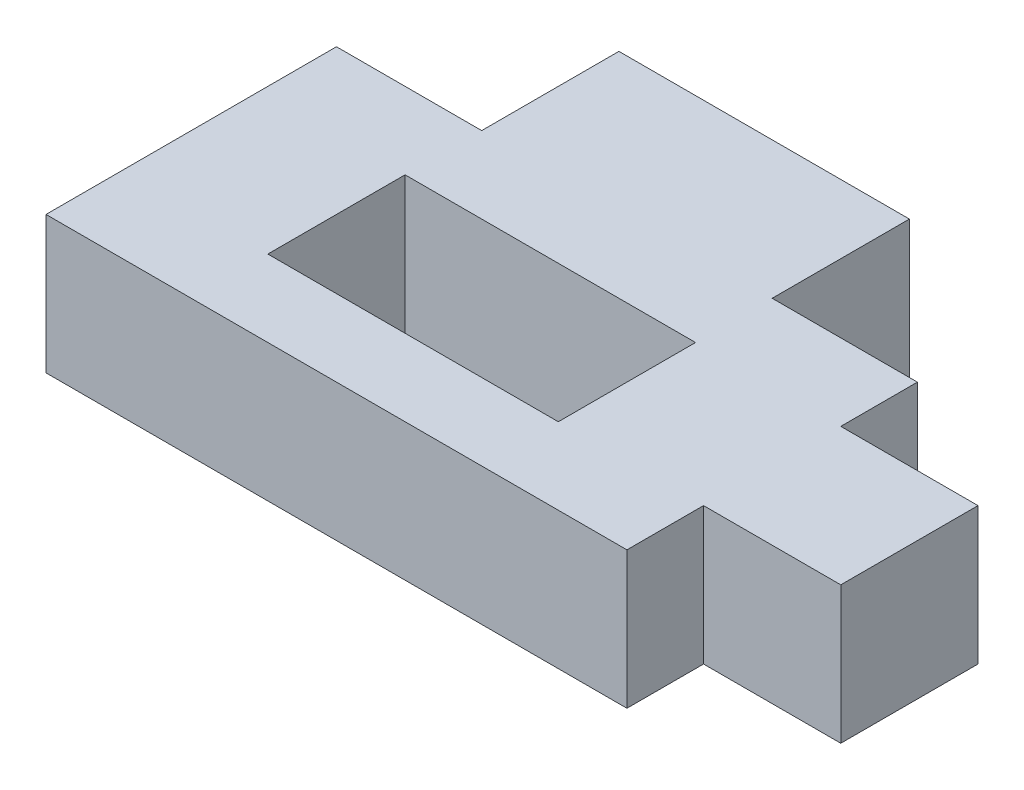
SolidWorks part; units mm, degrees
ref_plane "Front Plane" through (0, 0, 0) normal (0, 0, 1) x (1, 0, 0)
ref_plane "Top Plane" through (0, 0, 0) normal (0, 1, 0) x (1, 0, 0)
ref_plane "Right Plane" through (0, 0, 0) normal (1, 0, 0) x (0, 0, -1)
sketch "Sketch1" plane through (0, 0, 0) normal (0, 1, 0) x (1, 0, 0)
  line L0 (3.175, 3.175) -> (6.35, 3.175)
  line L1 (-3.175, -1.5) -> (3.175, -1.5)
  line L2 (-3.175, -1.5) -> (-3.175, 1.5)
  line L3 (-3.175, 1.5) -> (3.175, 1.5)
  line L4 (3.175, -1.5) -> (3.175, 1.5)
  line L5 (-3.175, -1.5) -> (3.175, 1.5) construction
  line L6 (-3.175, 1.5) -> (3.175, -1.5) construction
  line L7 (-6.35, -3.175) -> (6.35, -3.175)
  line L8 (-6.35, -3.175) -> (-6.35, 3.175)
  line L9 (-6.35, 3.175) -> (-3.175, 3.175)
  line L10 (6.35, -3.175) -> (6.35, -1.5)
  line L11 (-6.35, -3.175) -> (6.35, 3.175) construction
  line L12 (-6.35, 3.175) -> (6.35, -3.175) construction
  line L13 (-3.175, 6.175) -> (3.175, 6.175)
  line L14 (-3.175, 6.175) -> (-3.175, 3.175)
  line L16 (3.175, 6.175) -> (3.175, 3.175)
  line L17 (-3.175, 6.175) -> (3.175, 3.175) construction
  line L18 (-3.175, 3.175) -> (3.175, 6.175) construction
  line L19 (9.35, -1.5) -> (6.35, -1.5)
  line L20 (9.35, -1.5) -> (9.35, 1.5)
  line L21 (9.35, 1.5) -> (6.35, 1.5)
  line L23 (9.35, -1.5) -> (6.35, 1.5) construction
  line L24 (9.35, 1.5) -> (6.35, -1.5) construction
  line L25 (6.35, 1.5) -> (6.35, 3.175)
  point P0 (0, 0)
  point P6 (0, 0)
  point P11 (0, 4.675)
  point P16 (7.85, 0)
  point P21 (0, 5.0333)
  point P22 (0, 0)
  point P23 (7.943, 0)
  point P24 (0, 0)
  dimension "D1" = 3
  dimension "D2" = 6.35
  dimension "D3" = 12.7
  dimension "D4" = 6.35
  dimension "D5" = 6.35
  dimension "D6" = 3
  dimension "D7" = 3
  dimension "D8" = 3
extrude "Boss-Extrude1" add sketch "Sketch1" along normal mid plane 3
